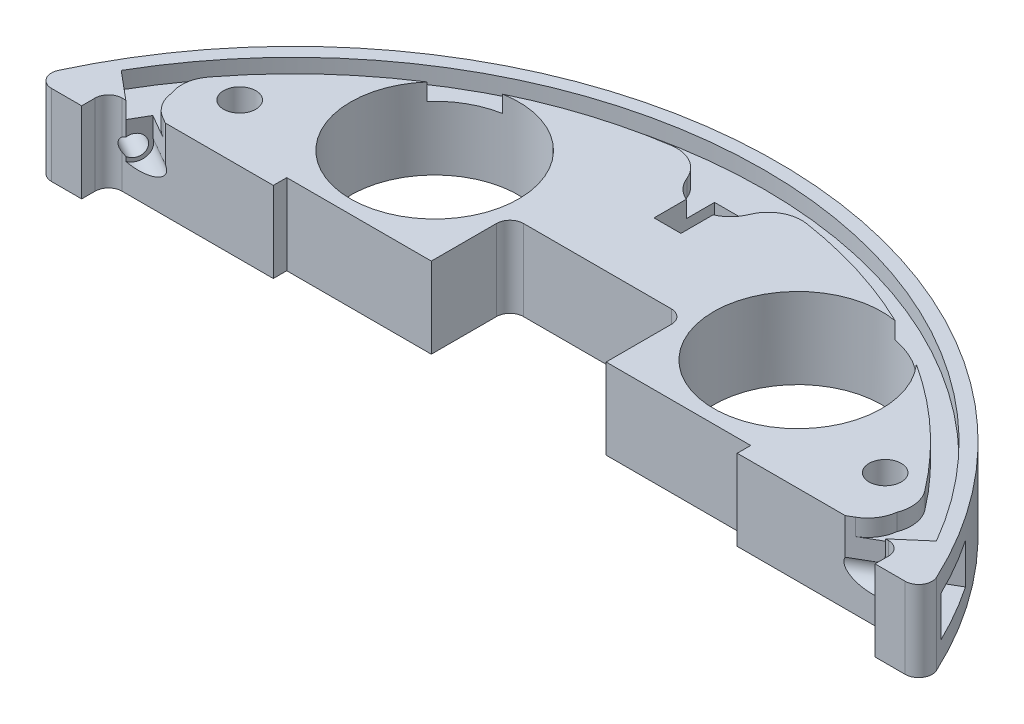
SolidWorks part; units mm, degrees
material "ABS"
ref_plane "Front Plane" through (0, 0, 0) normal (0, 0, 1) x (1, 0, 0)
ref_plane "Top Plane" through (0, 0, 0) normal (0, 1, 0) x (1, 0, 0)
ref_plane "Right Plane" through (0, 0, 0) normal (1, 0, 0) x (0, 0, -1)
sketch "Sketch1" plane through (0, 0, 0) normal (0, 1, 0) x (1, 0, 0)
  line L0 (0, -85) -> (-32.2211, -64.3879) construction
  line L1 (0, -85) -> (0, 0) construction
  arc A0 (36.2245, -62.2237) -> (-36.2245, -62.2237) centre (0, 0) ccw
  arc A1 (29.8119, -61.0352) -> (-29.8119, -61.0352) centre (0, -85) ccw
  arc A2 (36.2245, -62.2237) -> (29.8119, -61.0352) centre (33.7089, -57.9026) cw
  arc A3 (-29.8119, -61.0352) -> (-36.2245, -62.2237) centre (-33.7089, -57.9026) cw
  dimension "D1" = 144
  dimension "D2" = 76.5
  dimension "D4" = 5
  dimension "D3" = 85
extrude "Boss-Extrude1" add sketch "Sketch1" along normal mid plane 12
sketch "solenoid placement" plane through (0, 6, 0) normal (0, 1, 0) x (1, 0, 0)
  line L0 (0, 0) -> (0, -36) construction
  line L5 (-19, -36) -> (19, -36)
  line L7 (19, -36) -> (19, 28)
  line L9 (19, 28) -> (-19, 28)
  line L11 (-19, 28) -> (-19, -36)
  circle A1 centre (0, 0) radius 72 construction
  arc A2 (36.2245, -62.2237) -> (-36.2245, -62.2237) centre (0, 0) ccw construction
  dimension "D1" = 36
  dimension "D2" = 64
  dimension "D3" = 38
extrude "Cut-Extrude1" cut sketch "solenoid placement" against normal through all
sketch "Sketch4" plane through (0, 6, 0) normal (0, 1, 0) x (1, 0, 0)
  line L1 (-13, 28) -> (13, 28)
  line L2 (-13, 28) -> (-13, 43.2)
  line L4 (13, 28) -> (13, 43.2)
  line L5 (11, 45.2) -> (-11, 45.2)
  line L6 (19, 28) -> (-19, 28) construction
  arc A0 (11, 45.2) -> (13, 43.2) centre (11, 43.2) cw
  arc A1 (-11, 45.2) -> (-13, 43.2) centre (-11, 43.2) ccw
  point P6 (0, 28)
  dimension "D1" = 2
  dimension "D2" = 26
  dimension "D3" = 17.2
extrude "Cut-Extrude4" cut sketch "Sketch4" against normal through all
sketch "Sketch5" plane through (0, 6, 0) normal (0, 1, 0) x (1, 0, 0)
  line L0 (0, 0) -> (0, 72) construction
  arc A0 (36.2245, -62.2237) -> (-36.2245, -62.2237) centre (0, 0) ccw construction
  circle A1 centre (27, 48) radius 12.5
  circle A3 centre (-27, 48) radius 12.5
  dimension "D3" = 25
  dimension "D1" = 27
  dimension "D2" = 48
extrude "Cut-Extrude5" cut sketch "Sketch5" against normal through all
sketch "Sketch6" plane through (0, 6, 0) normal (0, 1, 0) x (1, 0, 0)
  line L0 (0, 0) -> (0, 72) construction
  arc A0 (36.2245, -62.2237) -> (-36.2245, -62.2237) centre (0, 0) ccw construction
  circle A1 centre (48, 40) radius 2.4
  circle A6 centre (-48, 40) radius 2.4
  dimension "D3" = 4.8
  dimension "D1" = 48
  dimension "D2" = 40
extrude "Cut-Extrude6" cut sketch "Sketch6" against normal through all
sketch "Sketch3" plane through (0, 6, 0) normal (0, 1, 0) x (1, 0, 0)
  line L1 (-72, -31.5) -> (72, -31.5) construction
  line L2 (-72, -31.5) -> (-72, 27.5)
  line L3 (-59, 31.5) -> (0, 31.5)
  line L4 (72, -31.5) -> (72, 27.5)
  line L5 (0, -31.5) -> (0, 31.5) construction
  line L6 (72, 27.5) -> (59, 27.5)
  line L9 (0, 31.5) -> (59, 31.5)
  line L10 (-72, -31.5) -> (-72, -101.6464)
  line L11 (72, -31.5) -> (72, -101.6464)
  line L12 (72, -101.6464) -> (-72, -101.6464)
  line L13 (59, 27.5) -> (59, 31.5)
  line L14 (-59, 27.5) -> (-59, 31.5)
  line L15 (-72, 27.5) -> (-59, 27.5)
  arc A0 (36.2245, -62.2237) -> (-36.2245, -62.2237) centre (0, 0) ccw construction
  point P0 (0, 0)
  dimension "D2" = 13
  dimension "D1" = 63
  dimension "D3" = 4
extrude "Cut-Extrude3" cut sketch "Sketch3" against normal through all
sketch "Sketch7" plane through (0, 0, 0) normal (0, 1, 0) x (1, 0, 0)
  line L0 (0, 0) -> (62.3538, 36) construction
  line L1 (0, 0) -> (-62.3538, 36) construction
  line L2 (0, 0) -> (0, 72) construction
  arc A0 (0, 72) -> (62.3538, 36) centre (0, 0) cw construction
  arc A1 (0, 72) -> (-62.3538, 36) centre (0, 0) ccw construction
  arc A2 (66.5413, 27.5) -> (-66.5413, 27.5) centre (0, 0) ccw construction
  dimension "D1" = 120
fillet "Fillet1" radius 2 4 edges at (-66.5413, 0, -27.5) (-59, 0, -31.5) (59, 0, -31.5) (66.5413, 0, -27.5)
sketch "Sketch8" plane through (0, 0, 0) normal (0, 1, 0) x (1, 0, 0)
  line L0 (5, 71.8262) -> (5, 68.8262)
  line L1 (0, 0) -> (64.7033, 31.583) construction
  line L2 (64.7033, 31.583) -> (59.7033, 40.2432) construction
  line L3 (64.7033, 31.583) -> (62.1052, 30.083)
  line L4 (62.1052, 30.083) -> (57.1052, 38.7432)
  line L5 (59.7033, 40.2432) -> (57.1052, 38.7432)
  line L6 (0, 0) -> (59.7033, 40.2432) construction
  line L7 (5, 68.8262) -> (-5, 68.8262)
  line L8 (-5, 71.8262) -> (-5, 68.8262)
  line L9 (5, 71.8262) -> (-5, 71.8262) construction
  line L10 (-59.7033, 40.2432) -> (-57.1052, 38.7432)
  line L11 (-57.1052, 38.7432) -> (-62.1052, 30.083)
  line L12 (-64.7033, 31.583) -> (-62.1052, 30.083)
  line L13 (-59.7033, 40.2432) -> (-64.7033, 31.583) construction
  arc A0 (59.7033, 40.2432) -> (64.7033, 31.583) centre (0, 0) cw
  arc A2 (-5, 71.8262) -> (5, 71.8262) centre (0, 0) cw
  arc A3 (-64.7033, 31.583) -> (-59.7033, 40.2432) centre (0, 0) cw
  point P4 (62.3538, 36)
  point P10 (-62.3538, 36)
  point P18 (0, 0)
  dimension "D1" = 10
  dimension "D2" = 3
extrude "Cut-Extrude7" cut sketch "Sketch8" against normal mid plane 6
sketch "Sketch10" plane through (0, 6, 0) normal (0, 1, 0) x (1, 0, 0)
  line L0 (0, 0) -> (0, 65) construction
  circle A0 centre (0, 65) radius 5
  dimension "D2" = 10
  dimension "D1" = 65
extrude "Cut-Extrude9" cut sketch "Sketch10" against normal blind 2.5
sketch "Sketch11" plane through (0, 6, 0) normal (0, 1, 0) x (1, 0, 0)
  line L1 (34.5, -33.5) -> (-34.5, -33.5)
  line L2 (34.5, -33.5) -> (34.5, 33.5)
  line L3 (34.5, 33.5) -> (-34.5, 33.5)
  line L4 (-34.5, -33.5) -> (-34.5, 33.5)
  line L5 (34.5, -33.5) -> (-34.5, 33.5) construction
  line L6 (34.5, 33.5) -> (-34.5, -33.5) construction
  point P0 (0, 0)
  dimension "D1" = 67
  dimension "D2" = 69
extrude "Cut-Extrude10" cut sketch "Sketch11" against normal through all
sketch "Sketch13" plane through (-59.6052, 0, -34.4131) normal (-0.866, 0, -0.5) x (-0.5, 0, 0.866)
  circle A0 centre (0, 0) radius 1.55
  dimension "D1" = 3.1
extrude "Cut-Extrude11" cut sketch "Sketch13" against normal blind 4.2
sketch "Sketch14" plane through (-55.9679, 0, -32.3131) normal (-0.866, 0, -0.5) x (-0.5, 0, 0.866)
  circle A0 centre (0, 0) radius 2.1
  dimension "D1" = 4.2
extrude "Cut-Extrude12" cut sketch "Sketch14" against normal blind 9
sketch "Sketch15" plane through (-55.9679, 0, -32.3131) normal (0.866, 0, 0.5) x (0.5, 0, -0.866)
  line L1 (-2, 0) -> (2, 0)
  line L2 (-2, 0) -> (-2, 10.8827)
  line L3 (-2, 10.8827) -> (2, 10.8827)
  line L4 (2, 0) -> (2, 10.8827)
  point P0 (0, 0)
  dimension "D1" = 4
extrude "Cut-Extrude13" cut sketch "Sketch15" along normal blind 9
pattern_circular "CirPattern1" count 3 over 120 about axis through (0, 6, 0) along (0, -1, 0) of "Cut-Extrude11", "Cut-Extrude12", "Cut-Extrude13"
sketch "Sketch16" plane through (0, 6, 0) normal (0, 1, 0) x (1, 0, 0)
  line L0 (0, 0) -> (-62.3538, 36) construction
  line L1 (0, 0) -> (62.3538, 36) construction
  line L2 (-56.4374, 31.5) -> (-54.9679, 34.0451) construction
  line L4 (-56.4374, 31.5) -> (-60.6218, 35)
  line L5 (3.5, 65) -> (-3.5, 65)
  line L6 (3.5, 65) -> (3.5, 66.9085)
  line L7 (-53.9374, 35.8301) -> (-55.6706, 37.2799)
  line L8 (-3.5, 65) -> (-3.5, 66.9085)
  line L9 (56.4775, 31.4305) -> (60.6218, 35)
  line L10 (53.9775, 35.7607) -> (55.6964, 37.2412)
  line L12 (54.9679, 34.0451) -> (56.4374, 31.5) construction
  line L13 (-53.9374, 35.8301) -> (-56.4374, 31.5)
  line L14 (53.9775, 35.7607) -> (56.4775, 31.4305)
  arc A0 (60.6218, 35) -> (-60.6218, 35) centre (0, 0) ccw
  arc A1 (55.6964, 37.2412) -> (3.5, 66.9085) centre (0, 0) ccw
  arc A2 (2, 60.4174) -> (-2, 60.4174) centre (0, 65) ccw construction
  arc A3 (-3.5, 66.9085) -> (-55.6706, 37.2799) centre (0, 0) ccw
  arc A4 (59, 29.5) -> (57, 31.5) centre (57, 29.5) ccw construction
  point P15 (0, 65)
  dimension "D1" = 3
  dimension "D2" = 140
  dimension "D3" = 7
  dimension "D4" = 5
  dimension "D5" = 5
extrude "Cut-Extrude14" cut sketch "Sketch16" against normal blind 2.5
fillet "Fillet2" radius 5 6 edges at (55.6964, 4.75, -37.2412) (-55.6706, 4.75, -37.2799) (54.9679, 4.75, -34.0451) (-54.9679, 4.75, -34.0451) (4.6497, 4.75, -66.8385) (-4.6497, 4.75, -66.8385)
equation "\"smallPulleyTeeth\"= 30"
equation "\"largePulleyTeeth\"= 30"
equation "\"eighthThick\"= 3.0mm"
equation "\"sixteenthThick\" = 1.7mm"
equation "\"quarterThick\"=6.0mm"
equation "\"OD\" = 145mm"
equation "\"puckAngle\" = 60.5deg"
equation "\"puckDiam\" = 76.5mm"
equation "\"D2@Sketch1\"=\"puckDiam\""
equation "\"D1@Boss-Extrude1\"=\"eighthThick\"*4"
equation "\"axlePress\" = 5.9mm"
equation "\"press\" = 0.2mm"
equation "\"wheelClear\" = 0.3mm"
equation "\"10-32clear\" = 4.8mm"
equation "\"6-32clear\" = 3.3mm"
equation "\"8-32clear\" = 4.0mm"
equation "\"wheelHeight\" = 22mm"
equation "\"wheelWell\" = 65mm"
equation "\"puckDist\" = 85mm"
equation "\"scoopFillet\" = 5mm"
equation "\"4-40clear\" = 3.0mm"
equation "\"D3@Sketch1\"=\"puckDist\""
equation "\"D4@Sketch1\"=\"scoopFillet\""
equation "\"D3@Sketch6\"=\"10-32clear\""
equation "\"D2@Sketch8\"=\"eighthThick\""
equation "\"10-32tap\" = 4.45mm"
equation "\"ledSmall\" = 3.1mm"
equation "\"ledLarge\" = 4.2mm"
equation "\"ledLength\" = 4.2mm"
equation "\"D1@Sketch13\"=\"ledSmall\""
equation "\"D1@Cut-Extrude11\"=\"ledLength\""
equation "\"D1@Sketch14\"=\"ledLarge\""
